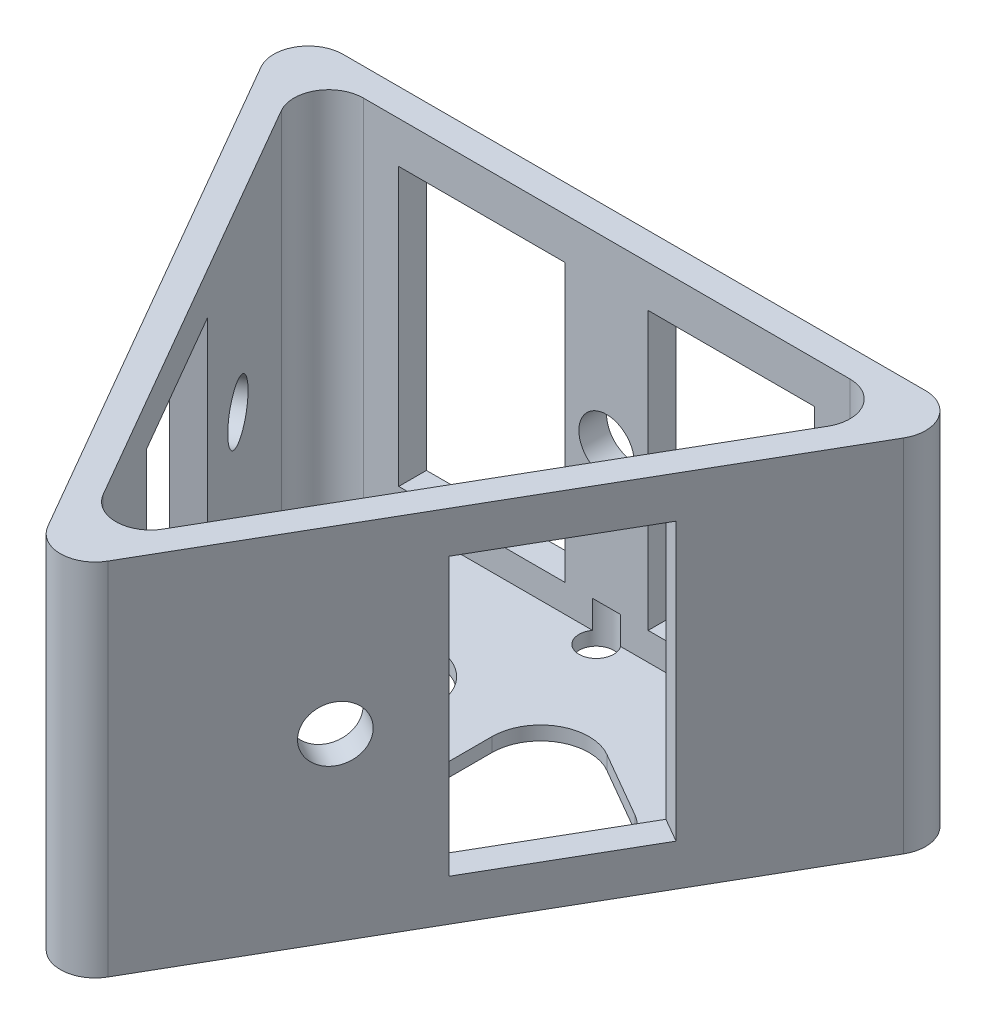
SolidWorks part; units mm, degrees
ref_plane "Front Plane" through (0, 0, 0) normal (0, 0, 1) x (1, 0, 0)
ref_plane "Top Plane" through (0, 0, 0) normal (0, 1, 0) x (1, 0, 0)
ref_plane "Right Plane" through (0, 0, 0) normal (1, 0, 0) x (0, 0, -1)
sketch "Sketch1" plane through (0, 0, 0) normal (0, 1, 0) x (1, 0, 0)
  line L0 (-55.0808, 36.1982) -> (-4.3714, 36.1982)
  line L1 (-4.3714, 36.1982) -> (-29.7261, -7.7174)
  line L2 (-55.0808, 36.1982) -> (-29.7261, -7.7174)
  line L3 (-51.6167, 34.1982) -> (-7.8355, 34.1982)
  line L4 (-7.8355, 34.1982) -> (-29.7261, -3.7174)
  line L5 (-51.6167, 34.1982) -> (-29.7261, -3.7174)
  dimension "D1" = 2
  dimension "D2" = 50.7094
extrude "Boss-Extrude1" add sketch "Sketch1" along normal blind 26
fillet "Fillet1" radius 2.5 6 edges at (-29.7261, 13, 3.7174) (-29.7261, 13, 7.7174) (-4.3714, 13, -36.1982) (-7.8355, 13, -34.1982) (-51.6167, 13, -34.1982) (-55.0808, 13, -36.1982)
sketch "Sketch2" plane through (-25.6363, 0, 14.8011) normal (-0.866, 0, 0.5) x (0.5, 0, 0.866)
  line L0 (-54.5588, 26) -> (-12.5097, 0) construction
  line L1 (-12.5097, 26) -> (-54.5588, 0) construction
  line L2 (-33.5343, 13) -> (-30.5343, 13) construction
  line L8 (-33.5343, 13) -> (-42.5343, 13) construction
  line L13 (-36.5343, 3) -> (-24.5343, 3)
  line L14 (-36.5343, 3) -> (-36.5343, 23)
  line L16 (-36.5343, 23) -> (-24.5343, 23)
  line L17 (-24.5343, 3) -> (-24.5343, 23)
  line L18 (-36.5343, 3) -> (-24.5343, 23) construction
  line L19 (-36.5343, 23) -> (-24.5343, 3) construction
  circle A1 centre (-42.5343, 13) radius 2
  dimension "D1" = 12
  dimension "D2" = 20
extrude "Cut-Extrude1" cut sketch "Sketch2" against normal up to next contours A1 | L13 L17 L16 L14 region at (-40.9034, 13, -11.6423) region at (-46.9034, 13, -22.0346)
sketch "Sketch3" plane through (-18.9528, 0, -10.9424) normal (0.866, 0, 0.5) x (0.5, 0, -0.866)
  line L0 (-17.2164, 26) -> (24.8327, 0) construction
  line L1 (-17.2164, 0) -> (24.8327, 26) construction
  line L2 (3.8082, 13) -> (6.8082, 13) construction
  line L13 (3.8082, 13) -> (-5.1918, 13) construction
  line L16 (0.8082, 3) -> (12.8082, 3)
  line L21 (0.8082, 3) -> (0.8082, 23)
  line L22 (0.8082, 23) -> (12.8082, 23)
  line L23 (12.8082, 3) -> (12.8082, 23)
  line L24 (0.8082, 3) -> (12.8082, 23) construction
  line L25 (0.8082, 23) -> (12.8082, 3) construction
  circle A2 centre (-5.1918, 13) radius 2
  dimension "D3" = 3
  dimension "D1" = 12
  dimension "D2" = 20
extrude "Cut-Extrude2" cut sketch "Sketch3" against normal up to next contours L16 L23 L0 L21 | L0 L23 L1 L21 | L1 L23 L22 L21 | A2 | L21 L1 L13 | L21 L13 L0
sketch "Sketch4" plane through (0, 0, -36.1982) normal (0, 0, -1) x (-1, 0, 0)
  line L0 (8.7015, 26) -> (50.7507, 0) construction
  line L1 (50.7507, 26) -> (8.7015, 0) construction
  line L20 (29.7261, 13) -> (20.7261, 13) construction
  line L22 (29.7261, 13) -> (38.7261, 13) construction
  line L23 (14.7261, 3) -> (26.7261, 3)
  line L24 (14.7261, 3) -> (14.7261, 23)
  line L25 (14.7261, 23) -> (26.7261, 23)
  line L26 (26.7261, 3) -> (26.7261, 23)
  line L27 (14.7261, 3) -> (26.7261, 23) construction
  line L28 (14.7261, 23) -> (26.7261, 3) construction
  line L30 (32.7261, 3) -> (44.7261, 3)
  line L31 (32.7261, 3) -> (32.7261, 23)
  line L32 (32.7261, 23) -> (44.7261, 23)
  line L33 (44.7261, 3) -> (44.7261, 23)
  line L34 (32.7261, 3) -> (44.7261, 23) construction
  line L35 (32.7261, 23) -> (44.7261, 3) construction
  circle A3 centre (29.7261, 13) radius 2
  dimension "D1" = 12
  dimension "D2" = 12
  dimension "D3" = 20
  dimension "D4" = 20
extrude "Cut-Extrude3" cut sketch "Sketch4" against normal up to next contours L23 L26 L1 L24 | L1 L26 L0 L24 | L0 L26 L25 L24 | L30 L33 L0 L31 | L0 L33 L1 L31 | L1 L33 L32 L31 | L1 A3 L0 | L0 A3 L22 | L22 A3 L1 | L1 A3 L0 | L0 A3 L20 | L20 A3 L1
sketch "Sketch5" plane through (0, 0, 0) normal (0, -1, 0) x (1, 0, 0)
  line L6 (-29.7261, -34.1982) -> (-29.7261, -33.4595)
  line L15 (-30.7261, -35.1915) -> (-49.2735, -24.4832) construction
  line L16 (-12.1656, -34.1982) -> (-47.2866, -34.1982) construction
  line L17 (-31.7261, -34.1982) -> (-31.7261, -33.4595) construction
  line L18 (-29.7261, -33.4595) -> (-45.8242, -24.1653)
  line L19 (-30.7261, -31.7274) -> (-9.4606, -19.4498) construction
  line L24 (-29.7261, -33.4595) -> (-13.628, -24.1653)
  line L25 (-31.7261, -29.9954) -> (-44.8242, -22.4332)
  line L26 (-27.7261, -34.6142) -> (-12.628, -25.8973)
  line L27 (-27.7261, -34.1982) -> (-27.7261, -34.6142)
  line L28 (-31.7261, -34.6142) -> (-46.8242, -25.8973)
  line L32 (-27.7261, -29.9954) -> (-14.628, -22.4332)
  line L33 (-31.7261, -34.1982) -> (-31.7261, -34.6142)
  line L34 (-49.4516, -30.4482) -> (-31.8912, -0.0326)
  line L35 (-27.561, -0.0326) -> (-10.0006, -30.4482)
  line L36 (-12.1656, -34.1982) -> (-47.2866, -34.1982)
  line L37 (-28.7261, -31.7274) -> (-47.2735, -21.0191) construction
  line L38 (-28.7261, -35.1915) -> (-7.4606, -22.9139) construction
  line L39 (-27.7261, -34.1982) -> (-27.7261, -33.4595) construction
  line L40 (-29.7261, -33.4595) -> (-8.4606, -21.1819) construction
  line L41 (-29.7261, -33.4595) -> (-48.2735, -22.7511) construction
  line L42 (-29.7261, -33.4595) -> (-29.7261, 1.2174)
  line L43 (-27.7261, -29.9954) -> (-27.7261, 0.2174)
  line L44 (-31.7261, -29.9954) -> (-31.7261, 0.2174)
  line L45 (-31.7261, -33.4595) -> (-31.7261, 1.2174) construction
  line L46 (-27.7261, -33.4595) -> (-27.7261, 1.2174) construction
  circle A1 centre (-29.7261, -33.4595) radius 1.25
  arc A2 (-27.561, -0.0326) -> (-31.8912, -0.0326) centre (-29.7261, -1.2826) ccw construction
  arc A3 (-27.561, -0.0326) -> (-31.8912, -0.0326) centre (-29.7261, -1.2826) ccw
  line M22 (-27.561, -0.0326) -> (-10.0006, -30.4482)
  line M24 (-12.1656, -34.1982) -> (-47.2866, -34.1982)
  line M26 (-49.4516, -30.4482) -> (-31.8912, -0.0326)
  arc M27 (-31.8912, -0.0326) -> (-27.561, -0.0326) centre (-29.7261, -1.2826) cw
  dimension "D3" = 2
  dimension "D1" = 2
  dimension "D2" = 2
  dimension "D4" = 2
extrude "Boss-Extrude2" add sketch "Sketch5" against normal blind 1 contours A1 L18 L28 L33 L6 M26 M24 | A1 L42 L44 L25 L18 M27 M26 | A1 L24 L32 L43 L42 M22 M27 | A1 L6 L27 L26 L24 M24 M22 region at (-20.6928, 0, -29.3949) region at (-38.7594, 0, -29.3949) region at (-38.1281, 0, -28.1737) region at (-28.9128, 0, -32.0508)
fillet "Fillet3" radius 3.5 10 edges at (-12.628, 0.5, -25.8973) (-14.628, 0.5, -22.4332) (-44.8242, 0.5, -22.4332) (-46.8242, 0.5, -25.8973) (-31.7261, 0.5, 0.2174) (-27.7261, 0.5, 0.2174) (-27.7261, 0.5, -29.9954) (-31.7261, 0.5, -29.9954) (-27.0056, 0.5, -34.1982) (-32.4466, 0.5, -34.1982)
sketch "Sketch6" plane through (0, 0, 0) normal (0, -1, 0) x (1, 0, 0)
  circle A0 centre (-29.7261, -33.4595) radius 1.25
extrude "Cut-Extrude4" cut sketch "Sketch6" against normal blind 3
